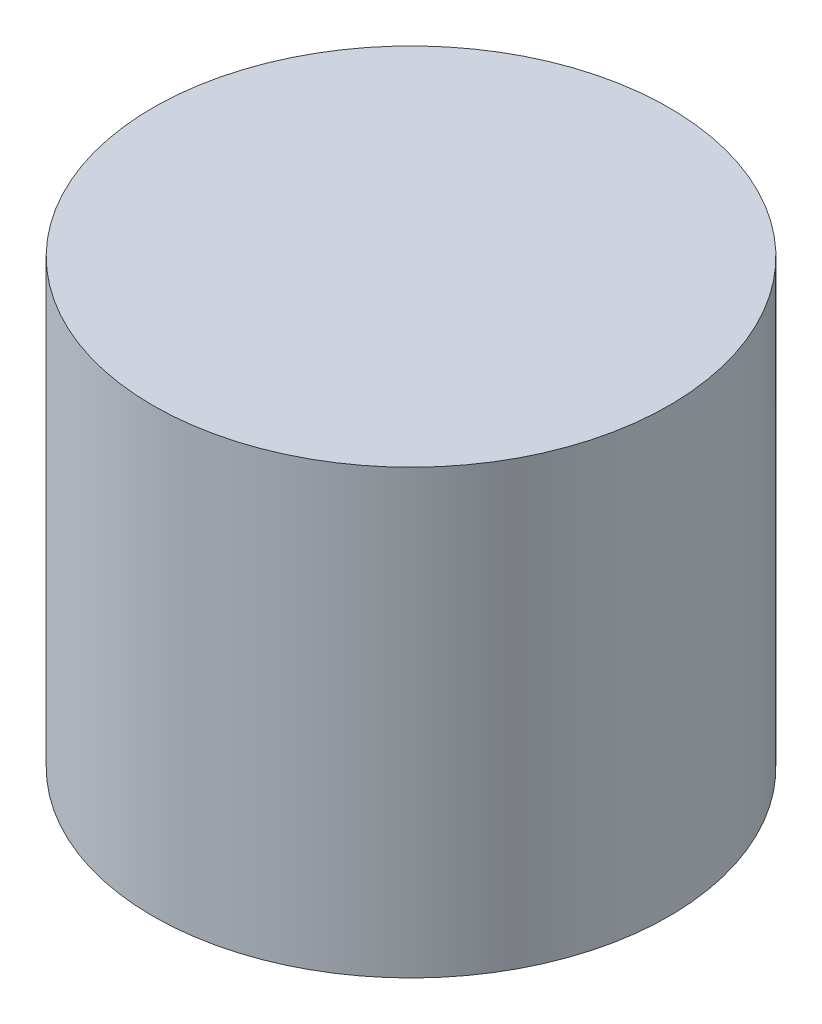
SolidWorks part; units mm, degrees
ref_plane "Front Plane" through (0, 0, 0) normal (0, 0, 1) x (1, 0, 0)
ref_plane "Top Plane" through (0, 0, 0) normal (0, 1, 0) x (1, 0, 0)
ref_plane "Right Plane" through (0, 0, 0) normal (1, 0, 0) x (0, 0, -1)
sketch "Sketch1" plane through (0, 0, 0) normal (0, 1, 0) x (1, 0, 0)
  circle A0 centre (0, 0) radius 17.5
  dimension "D1" = 35
extrude "Boss-Extrude1" add sketch "Sketch1" along normal blind 30
sketch "Sketch2" plane through (0, 0, 0) normal (1, 0, 0) x (0, 0, -1)
  line L0 (17.5, 0) -> (17.5, 30) construction
  line L1 (-17.5, 26) -> (17.5, 26)
  line L2 (-17.5, 26) -> (-17.5, 4)
  line L3 (-17.5, 4) -> (17.5, 4)
  line L4 (17.5, 26) -> (17.5, 4)
  line L5 (-17.5, 26) -> (17.5, 4) construction
  line L6 (-17.5, 4) -> (17.5, 26) construction
  line L7 (17.5, 30) -> (-17.5, 30) construction
  line L8 (0, 30) -> (0, 0) construction
  line L10 (-11.18, 26) -> (-11.18, 4)
  line L11 (-11.18, 4) -> (11.18, 4)
  line L12 (11.18, 4) -> (11.18, 26)
  line L13 (11.18, 26) -> (-11.18, 26)
  point P0 (0, 15)
  dimension "D1" = 22
  dimension "D2" = 22.36
  dimension "D3" = 11.18
extrude "Cut-Extrude1" cut sketch "Sketch2" against normal blind 30 contours L3 L12 L1 L10 region at (0, 15, 0)
